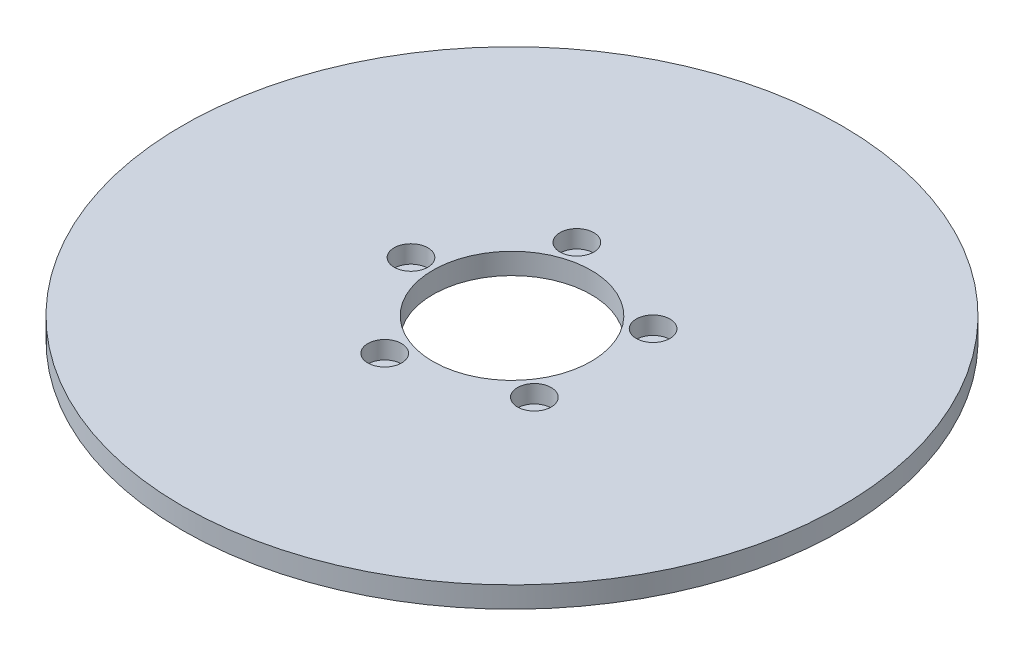
SolidWorks part; units mm, degrees
ref_plane "Front Plane" through (0, 0, 0) normal (0, 0, 1) x (1, 0, 0)
ref_plane "Top Plane" through (0, 0, 0) normal (0, 1, 0) x (1, 0, 0)
ref_plane "Right Plane" through (0, 0, 0) normal (1, 0, 0) x (0, 0, -1)
sketch "Sketch1" plane through (0, 0, 0) normal (0, 1, 0) x (1, 0, 0)
  circle A0 centre (0, 0) radius 62.5
  dimension "FLANGE_OD" = 125
extrude "Boss-Extrude1" add sketch "Sketch1" along normal blind 4
sketch "Sketch2" plane through (0, 0, 0) normal (0, 1, 0) x (1, 0, 0)
  circle A0 centre (0, 0) radius 15
  dimension "BORE_D" = 30
extrude "Cut-Extrude1" cut sketch "Sketch2" along normal through all
sketch "Sketch3" plane through (0, 4, 0) normal (0, 1, 0) x (1, 0, 0)
  circle A0 centre (0, 0) radius 19.1565 construction
  circle A1 centre (-19.1565, 0) radius 3.2014
  dimension "BOLT_D" = 6.4029
  dimension "BOLT_PCD" = 38.313
extrude "Cut-Extrude2" cut sketch "Sketch3" against normal blind 3.3608
pattern_circular "CirPattern1" count 5 over 360 about axis through (0, 0, 0) along (0, 1, 0) of "Cut-Extrude2"
